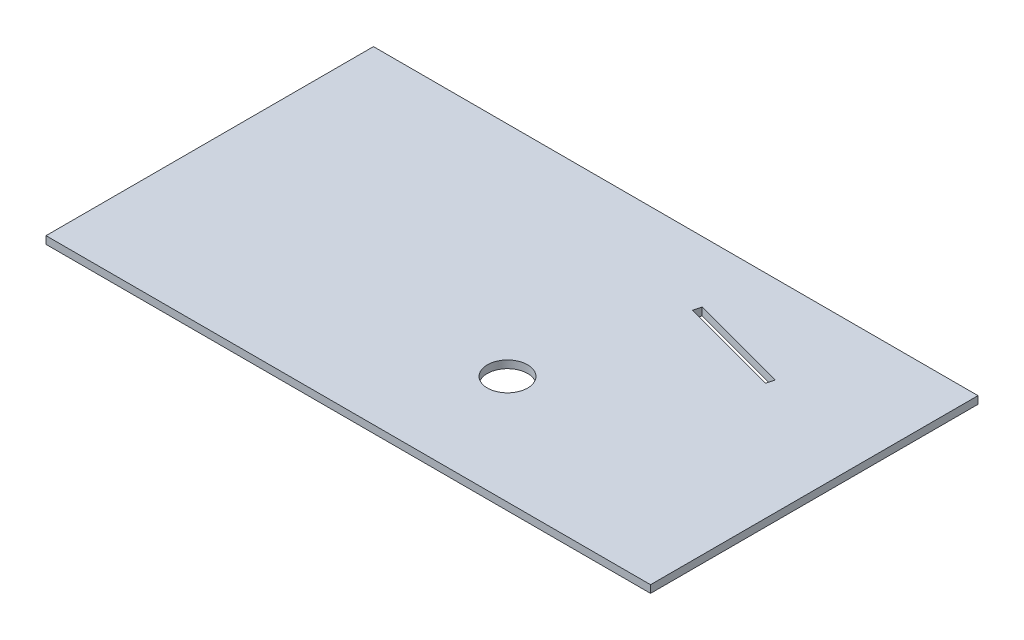
SolidWorks part; units mm, degrees
ref_plane "Front Plane" through (0, 0, 0) normal (0, 0, 1) x (1, 0, 0)
ref_plane "Top Plane" through (0, 0, 0) normal (0, 1, 0) x (1, 0, 0)
ref_plane "Right Plane" through (0, 0, 0) normal (1, 0, 0) x (0, 0, -1)
sketch "Sketch3" plane through (0, 0, 0) normal (0, 1, 0) x (1, 0, 0)
  line L1 (0, 0) -> (-839.8654, 0) construction
  line L2 (0, 0) -> (-451.1992, 260.5) construction
  line L5 (-524, 0) -> (-525.5875, 0)
  line L6 (277.6777, 444.3772) -> (277.6777, 446.248)
  circle A0 centre (0, 0) radius 254 construction
  arc A3 (277.6777, 444.3772) -> (-524, 0) centre (0, 0) ccw
  arc A4 (277.6777, 446.248) -> (-525.5875, 0) centre (0, 0) ccw
  arc A5 (278.5189, 445.7235) -> (-525.5875, 0) centre (0, 0) ccw construction
  dimension "D1" = 524
  dimension "D2" = 1.5875
  dimension "D4" = 122
  dimension "D5" = 508
  dimension "D3" = 30
extrude "Boss-Extrude1" add sketch "Sketch3" along normal blind 50.8
sketch "Sketch4" plane through (0, 50.8, 0) normal (0, 1, 0) x (1, 0, 0)
  line L5 (-889, 551.088) -> (635, 551.088)
  line L6 (-889, 551.088) -> (-889, -274.412)
  line L7 (-889, -274.412) -> (635, -274.412)
  line L8 (635, 551.088) -> (635, -274.412)
  dimension "D1" = 274.412
  dimension "D2" = 1524
  dimension "D3" = 825.5
  dimension "D4" = 635
extrude "Boss-Extrude2" add sketch "Sketch4" along normal blind 19.05 separate body
hole_wizard "Ø20.0mm Dowel Hole1" positions "Sketch6" profile "Sketch7" hole size "Ø20.0" standard "ANSI Metric" end condition through all
sketch "Sketch6" plane through (0, 50.8, 0) normal (0, -1, 0) x (-1, 0, 0)
  point P0 (0, 0)
sketch "Sketch7" plane through (0, 50.8, 0) normal (1, 0, 0) x (0, 0, -1)
  line L0 (0, 0) -> (0, 19.05)
  line L1 (0, 19.05) -> (50.8, 19.05)
  line L2 (50.8, 19.05) -> (50.8, 0)
  line L5 (50.8, 0) -> (0, 0)
  line L11 (0, -6.35) -> (0, 107.95) construction
  dimension "Thru Hole Dia." = 101.6
  dimension "Thru Hole Depth" = 19.05
ref_plane "Plane1" through (0, 0, 268.062) normal (0, 0, 1) x (1, 0, 0)
sketch "Sketch8" plane through (0, 0, 0) normal (0, 0, 1) x (1, 0, 0)
  line L0 (-524, 50.8) -> (-524, 0) construction
  line L1 (-525.5875, 50.8) -> (-524, 50.8)
  line L2 (-525.5875, 50.8) -> (-525.5875, 0)
  line L3 (-525.5875, 0) -> (-524, 0)
  line L4 (-524, 50.8) -> (-524, 0)
  line L5 (-525.5875, 50.8) -> (-525.5875, 0) construction
  line L6 (-525.5875, 0) -> (-524, 0) construction
  line L8 (-525.5875, 50.8) -> (-524, 50.8) construction
extrude "Boss-Extrude3" add sketch "Sketch8" along normal blind 204
sketch "Sketch9" plane through (0, 50.8, 0) normal (0, -1, 0) x (-1, 0, 0)
  line L0 (-94.0357, 396.6115) -> (-345.1764, 329.3185)
  line L1 (-345.1764, 329.3185) -> (-340, 310)
  line L2 (-340, 310) -> (-88.8593, 377.293)
  line L3 (-88.8593, 377.293) -> (-94.0357, 396.6115)
  line L6 (0, 0) -> (-635, 0) construction
  line L7 (-635, -274.412) -> (-635, 551.088) construction
  dimension "D1" = 260
  dimension "D2" = 20
  dimension "D3" = 15
  dimension "D4" = 340
  dimension "D5" = 310
extrude "Cut-Extrude1" cut sketch "Sketch9" against normal through all
sketch "Sketch10" plane through (0, 69.85, 0) normal (0, -1, 0) x (-1, 0, 0)
  line L0 (0, 0) -> (-545.6, 0) construction
  line L1 (0, 0) -> (277.6777, 444.3772) construction
  line L2 (0, 0) -> (195.5256, 509.3615) construction
  line L3 (0, 0) -> (94.7424, 537.3111) construction
  circle A0 centre (0, 0) radius 545.6 construction
  dimension "D1" = 11
  dimension "D2" = 11
ref_axis "WHEEL CENTER" through (-565.7508, 50.8, 0) along (1, 0, 0)
ref_plane "BASE CENTER" through (-127, 0, 0) normal (1, 0, 0) x (0, 0, -1)
sketch "Sketch11" plane through (0, 50.8, 0) normal (0, -1, 0) x (1, 0, 0)
  line L0 (240.5176, 138.2676) -> (268.3331, 149.5058)
  line L1 (268.3331, 149.5058) -> (296.8782, 78.8544)
  line L2 (296.8782, 78.8544) -> (269.0626, 67.6162)
  line L3 (269.0626, 67.6162) -> (240.5176, 138.2676)
  line L4 (-561.4964, -185.7671) -> (-532.9514, -256.4185)
  line L5 (-532.9514, -256.4185) -> (-505.1359, -245.1803)
  line L6 (-505.1359, -245.1803) -> (-533.6809, -174.5289)
  line L7 (-533.6809, -174.5289) -> (-561.4964, -185.7671)
  line L8 (-889, -259.242) -> (635, -259.242)
  line L9 (635, 274.412) -> (635, -551.088) construction
  line L10 (-889, -551.088) -> (-889, 274.412) construction
  line L11 (635, -551.088) -> (-889, -551.088) construction
  dimension "D1" = 30
  dimension "D2" = 30
  dimension "D3" = 291.846
